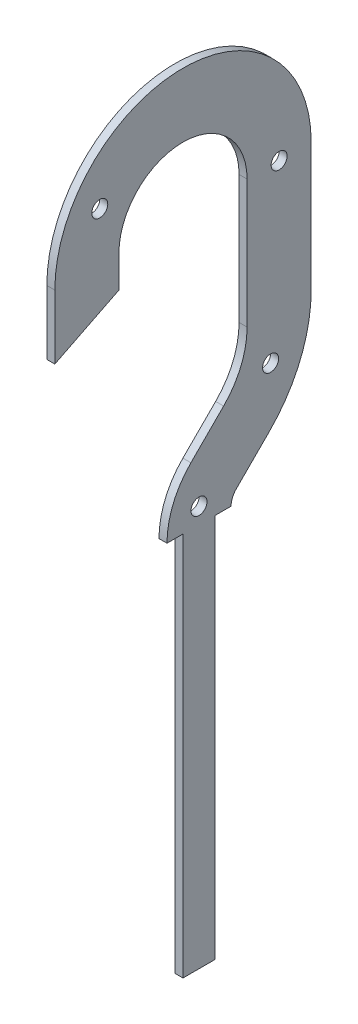
SolidWorks part; units mm, degrees
ref_plane "Front Plane" through (0, 0, 0) normal (0, 0, 1) x (1, 0, 0)
ref_plane "Top Plane" through (0, 0, 0) normal (0, 1, 0) x (1, 0, 0)
ref_plane "Right Plane" through (0, 0, 0) normal (1, 0, 0) x (0, 0, -1)
sketch "Sketch1" plane through (0, 0, 0) normal (1, 0, 0) x (0, 0, -1)
  line L0 (-50.8, 0) -> (-50.8, -25.4)
  line L2 (25.4, 0) -> (25.4, -50.8)
  line L4 (50.8, -50.8) -> (50.8, 0)
  line L5 (-6.35, 0) -> (-6.35, -103.13) construction
  line L6 (6.35, 0) -> (6.35, -103.13) construction
  line L7 (16.1006, -73.2506) -> (3.1306, -86.2206)
  line L8 (3.1306, -86.2206) -> (42.7043, -125.7943) construction
  line L9 (-25.4, 0) -> (-25.4, -12.7)
  line L10 (-50.8, -25.4) -> (-25.4, -12.7)
  line L11 (34.0612, -91.2112) -> (21.0911, -104.1812)
  line L12 (-6.35, -109.1089) -> (0, -109.1089)
  line L13 (0, -109.1089) -> (0, -261.5089)
  line L14 (0, -261.5089) -> (12.7, -261.5089)
  line L15 (12.7, -261.5089) -> (12.7, -109.1089)
  line L16 (12.7, -109.1089) -> (19.05, -109.1089)
  arc A0 (50.8, 0) -> (-50.8, 0) centre (0, 0) ccw
  arc A1 (25.4, 0) -> (-25.4, 0) centre (0, 0) ccw
  arc A2 (25.4, -50.8) -> (16.1006, -73.2506) centre (-6.35, -50.8) cw
  arc A3 (3.1306, -86.2206) -> (-6.35, -109.1089) centre (26.0189, -109.1089) ccw
  arc A4 (50.8, -50.8) -> (34.0612, -91.2112) centre (-6.35, -50.8) cw
  arc A5 (21.0911, -104.1812) -> (19.05, -109.1089) centre (26.0189, -109.1089) ccw
  dimension "D1" = 50.8
  dimension "D3" = 25.4
  dimension "D5" = 6.35
  dimension "D6" = 6.35
  dimension "D7" = 45
  dimension "D9" = 45
  dimension "D8" = 45
  dimension "D2" = 25.4
  dimension "D4" = 50.8
  dimension "D10" = 152.4
  dimension "D11" = 12.7
extrude "Boss-Extrude1" add sketch "Sketch1" along normal blind 3.175
sketch "Sketch2" plane through (3.175, 0, 0) normal (1, 0, 0) x (0, 0, -1)
  line L0 (25.4, 0) -> (25.4, -50.8) construction
  line L1 (22.9832, -62.9502) -> (55.7935, -76.5407) construction
  line L2 (-6.35, -109.1089) -> (0, -109.1089) construction
  circle A0 centre (38.1, 0) radius 3.175
  circle A1 centre (-32.9956, 19.05) radius 3.175
  arc A2 (38.1, 0) -> (-32.9956, 19.05) centre (0, 0) ccw construction
  circle A3 centre (34.7164, -67.8103) radius 3.175
  arc A4 (16.1006, -73.2506) -> (25.4, -50.8) centre (-6.35, -50.8) ccw construction
  circle A5 centre (6.35, -102.7589) radius 3.175
  dimension "D1" = 6.35
  dimension "D3" = 6.35
  dimension "D5" = 6.35
  dimension "D7" = 6.35
  dimension "D2" = 12.7
  dimension "D4" = 150
  dimension "D6" = 12.7
  dimension "D8" = 6.35
extrude "Cut-Extrude1" cut sketch "Sketch2" against normal through all
